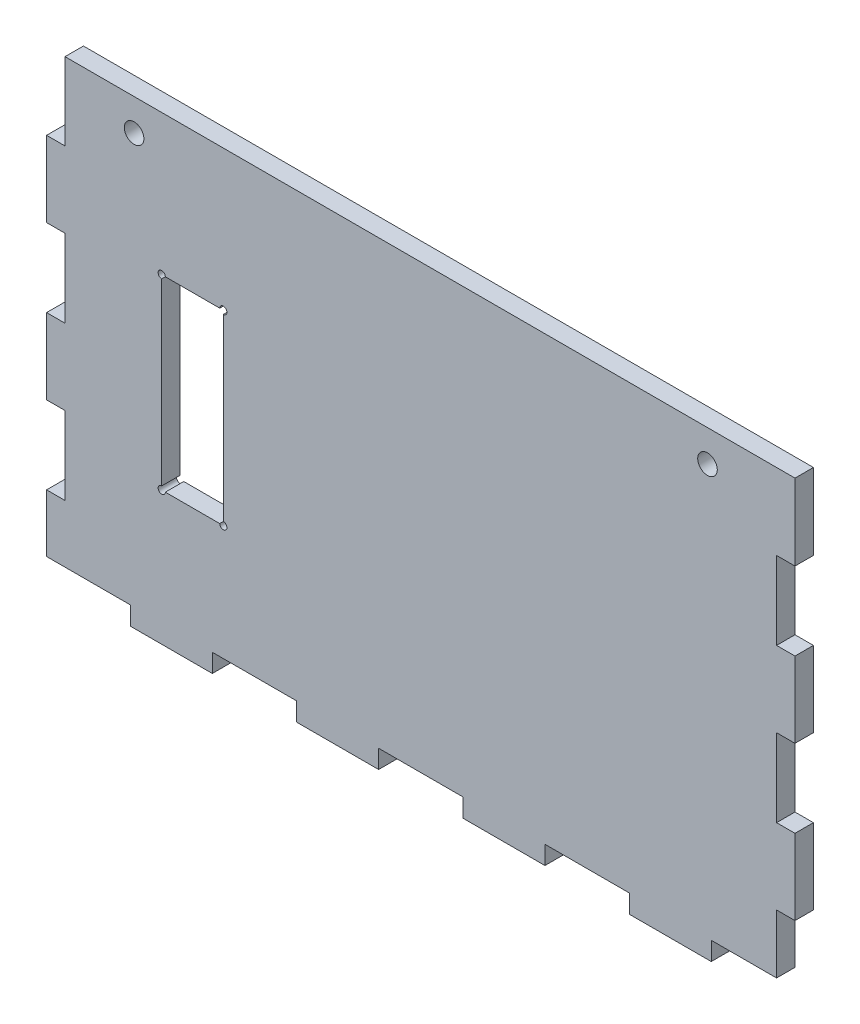
SolidWorks part; units mm, degrees
material "Acrylic (Medium-high impact)"
ref_plane "Front Plane" through (0, 0, 0) normal (0, 0, 1) x (1, 0, 0)
ref_plane "Top Plane" through (0, 0, 0) normal (0, 1, 0) x (1, 0, 0)
ref_plane "Right Plane" through (0, 0, 0) normal (1, 0, 0) x (0, 0, -1)
sketch "Sketch1" plane through (0, 0, 0) normal (0, 0, 1) x (1, 0, 0)
  line L1 (0, 0) -> (130, 0)
  line L2 (0, 0) -> (0, 80)
  line L3 (0, 80) -> (130, 80)
  line L4 (130, 0) -> (130, 80)
  dimension "D1" = 130
  dimension "D2" = 80
extrude "Boss-Extrude1" add sketch "Sketch1" along normal blind 3.2
sketch "Sketch2" plane through (0, 0, 3.2) normal (0, 0, 1) x (1, 0, 0)
  line L61 (14.4444, 3.2) -> (28.8889, 3.2) construction
  line L62 (0, 0) -> (14.4444, 0)
  line L67 (0, 0) -> (0, 3.2)
  line L72 (0, 3.2) -> (14.4444, 3.2)
  line L77 (14.4444, 0) -> (14.4444, 3.2)
  line L97 (28.8889, 0) -> (28.8889, 3.2)
  line L98 (28.8889, 0) -> (43.3333, 0)
  line L107 (43.3333, 0) -> (43.3333, 3.2)
  line L115 (28.8889, 3.2) -> (43.3333, 3.2)
  line L117 (43.3333, 3.2) -> (57.7778, 3.2) construction
  line L123 (57.7778, 0) -> (57.7778, 3.2)
  line L128 (57.7778, 0) -> (72.2222, 0)
  line L129 (72.2222, 0) -> (72.2222, 3.2)
  line L131 (57.7778, 3.2) -> (72.2222, 3.2)
  line L132 (72.2222, 3.2) -> (86.6667, 3.2) construction
  line L133 (86.6667, 0) -> (86.6667, 3.2)
  line L134 (86.6667, 0) -> (101.1111, 0)
  line L135 (101.1111, 0) -> (101.1111, 3.2)
  line L136 (86.6667, 3.2) -> (101.1111, 3.2)
  line L137 (101.1111, 3.2) -> (115.5556, 3.2) construction
  line L138 (115.5556, 0) -> (115.5556, 3.2)
  line L139 (115.5556, 0) -> (130, 0)
  line L142 (130, 0) -> (130, 80) construction
  line L143 (0, 80) -> (0, 0) construction
  line L144 (0, 13.3333) -> (3.2, 13.3333)
  line L145 (0, 13.3333) -> (0, 26.6667)
  line L146 (130, 3.2) -> (144.4444, 3.2) construction
  line L147 (0, 26.6667) -> (3.2, 26.6667)
  line L148 (3.2, 13.3333) -> (3.2, 26.6667)
  line L149 (3.2, 13.3333) -> (3.2, 0) construction
  line L150 (0, 40) -> (0, 53.3333)
  line L151 (0, 40) -> (3.2, 40)
  line L152 (3.2, 40) -> (3.2, 53.3333)
  line L153 (0, 53.3333) -> (3.2, 53.3333)
  line L154 (3.2, 40) -> (3.2, 26.6667) construction
  line L155 (0, 66.6667) -> (0, 80)
  line L156 (0, 66.6667) -> (3.2, 66.6667)
  line L157 (3.2, 66.6667) -> (3.2, 80)
  line L158 (0, 80) -> (3.2, 80)
  line L159 (3.2, 66.6667) -> (3.2, 53.3333) construction
  line L160 (130, 80) -> (0, 80) construction
  line L161 (126.8, 80) -> (126.8, 66.6667) construction
  line L162 (126.8, 40) -> (126.8, 26.6667)
  line L163 (126.8, 66.6667) -> (130, 66.6667)
  line L164 (126.8, 66.6667) -> (126.8, 53.3333)
  line L165 (126.8, 53.3333) -> (130, 53.3333)
  line L166 (130, 66.6667) -> (130, 53.3333)
  line L167 (126.8, 40) -> (130, 40)
  line L168 (130, 40) -> (130, 26.6667)
  line L169 (126.8, 26.6667) -> (130, 26.6667)
  line L170 (126.8, 53.3333) -> (126.8, 40) construction
  line L172 (126.8, 13.3333) -> (130, 13.3333)
  line L173 (130, 13.3333) -> (130, 0)
  line L175 (126.8, 26.6667) -> (126.8, 13.3333) construction
  line L183 (115.5556, 3.2) -> (130, 3.2) [skipped]
  line L184 (130, 0) -> (130, 3.2) [skipped]
  line L185 (126.8, 13.3333) -> (126.8, 3.2)
  line L186 (126.8, 3.2) -> (115.5556, 3.2)
  line L187 (126.8, 0) -> (130, 0) [skipped]
  line L188 (126.8, 13.3333) -> (126.8, 0) [skipped]
  dimension "D2" = 3.2
  dimension "D4" = 3.2
  dimension "D6" = 3.2
  dimension "D1" = 5
  dimension "D3" = 3
  dimension "D5" = 3
extrude "Cut-Extrude1" cut sketch "Sketch2" against normal through all
sketch "Sketch3" plane through (0, 0, 3.2) normal (0, 0, 1) x (1, 0, 0)
  line L0 (0, 66.6667) -> (0, 53.3333) construction
  line L1 (130, 80) -> (3.2, 80) construction
  line L2 (0, 66.6667) -> (130, 66.6667) construction
  line L3 (65, 66.6667) -> (65, 50066.6667) construction
  circle A0 centre (15.2, 74.5) radius 1.7
  circle A1 centre (114.8, 74.5) radius 1.7
  point P10 (65, 66.6667)
  dimension "D1" = 3.4
  dimension "D2" = 15.2
  dimension "D3" = 5.5
extrude "Cut-Extrude2" cut sketch "Sketch3" against normal up to next
sketch "Sketch4" plane through (0, 0, 0) normal (0, 0, -1) x (-1, 0, 0)
  line L0 (-3.2, 13.3333) -> (-3.2, 26.6667) construction
  line L1 (-30.075, 55.6) -> (-20.625, 55.6)
  line L2 (-30.7, 54.975) -> (-30.7, 23.825)
  line L3 (-30.075, 23.2) -> (-20.625, 23.2)
  line L4 (-20, 54.975) -> (-20, 23.825)
  line L5 (-43.3333, 3.2) -> (-28.8889, 3.2) construction
  arc A0 (-30.7, 23.825) -> (-30.075, 23.2) centre (-30.7, 23.2) ccw
  arc A1 (-20.625, 23.2) -> (-20, 23.825) centre (-20, 23.2) ccw
  arc A2 (-20, 54.975) -> (-20.625, 55.6) centre (-20, 55.6) ccw
  arc A3 (-30.075, 55.6) -> (-30.7, 54.975) centre (-30.7, 55.6) ccw
  point P16 (0, 0)
  point P17 (0, 0)
  point P18 (0, 0)
  point P19 (0, 0)
  point P20 (0, 0)
  point P21 (0, 0)
  point P22 (0, 0)
  point P23 (0, 0)
  point P24 (0, 0)
  dimension "D3" = 1.25
  dimension "D1" = 10.7
  dimension "D2" = 32.4
  dimension "D4" = 16.8
  dimension "D5" = 20
extrude "Cut-Extrude3" cut sketch "Sketch4" against normal up to next
other "Width tolerance" flip direction yes face at (1.6, 26.6667, 1.6) face at (1.6, 53.3333, 1.6) face at (1.6, 66.6667, 1.6) face at (1.6, 40, 1.6) face at (1.6, 13.3333, 1.6) face at (128.4, 66.6667, 1.6) face at (128.4, 40, 1.6) face at (128.4, 53.3333, 1.6) face at (128.4, 26.6667, 1.6) face at (128.4, 13.3333, 1.6) face at (101.1111, 1.6, 1.6) face at (115.5556, 1.6, 1.6) face at (86.6667, 1.6, 1.6) face at (72.2222, 1.6, 1.6) face at (43.3333, 1.6, 1.6) face at (57.7778, 1.6, 1.6) face at (28.8889, 1.6, 1.6) face at (14.4444, 1.6, 1.6) offset 0.1 parameters "D1"=0.1
equation "\"wall_thickness\"= 3.2mm"
equation "\"D1@Boss-Extrude1\"=\"wall_thickness\""
equation "\"slot_width_tolerance\"= 0.1mm"
equation "\"slot_depth\"= 3.2mm"
equation "\"D2@Sketch2\"=\"slot_depth\""
equation "\"D4@Sketch2\"=\"slot_depth\""
equation "\"D6@Sketch2\"=\"slot_depth\""
equation "\"D2@Sketch3\"=12.00mm+\"slot_depth\""
equation "\"D1@Width tolerance\"=\"slot_width_tolerance\""
